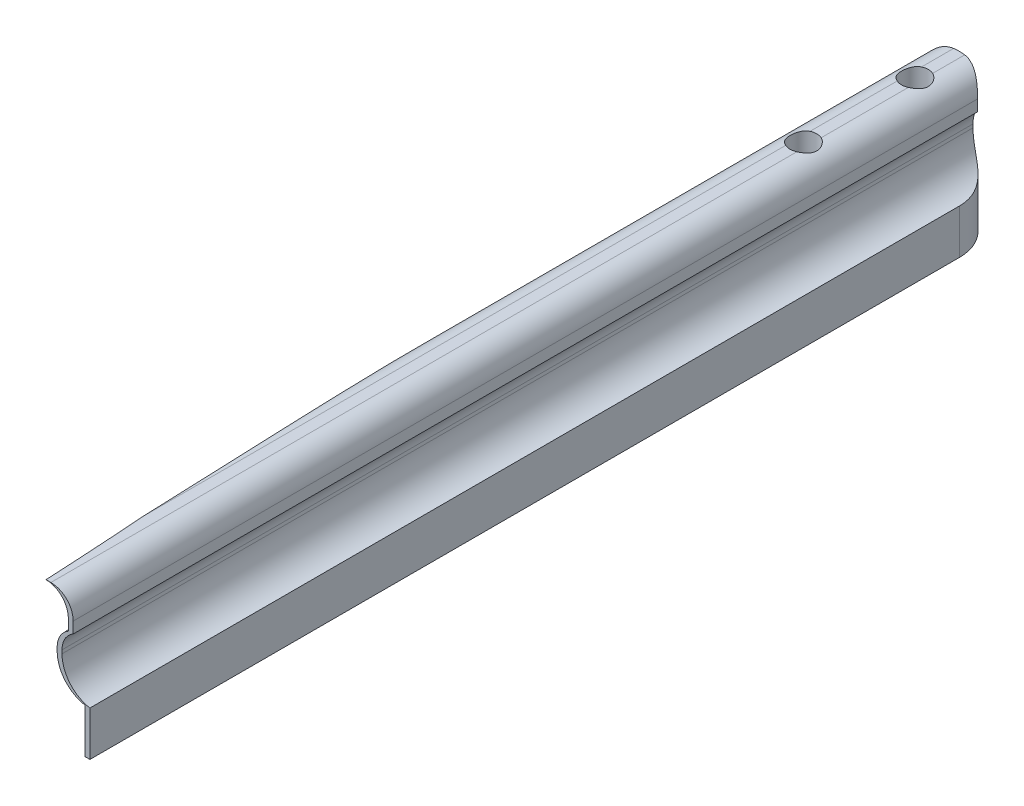
SolidWorks part; units mm, degrees
other "标注1"
sketch "草图3" plane through (-22.25, 4, -10) normal (-0.231, 0.6469, -0.7268) x (-0.9696, -0.2151, 0.1167)
other "标注2"
sketch "草图4" plane through (22.25, 8, -30) normal (0.0083, 0.0567, -0.9984) x (-0.9991, 0.0415, -0.0059)
ref_plane "前视基准面" through (0, 0, 0) normal (0, 0, 1) x (1, 0, 0)
ref_plane "上视基准面" through (0, 0, 0) normal (0, 1, 0) x (1, 0, 0)
ref_plane "右视基准面" through (0, 0, 0) normal (1, 0, 0) x (0, 0, -1)
other "Configuration Table"
sketch "草图1" plane through (0, 0, 0) normal (0, 1, 0) x (1, 0, 0)
  line L0 (-13.75, 12.5) -> (-13.75, -12.5)
  line L13 (-17.75, -12.5) -> (17.75, -12.5)
  line L21 (-17.75, -12.5) -> (-17.75, 12.5)
  line L22 (-17.75, 12.5) -> (17.75, 12.5)
  line L23 (17.75, -12.5) -> (17.75, 12.5)
  line L24 (-17.75, -12.5) -> (17.75, 12.5) construction
  line L25 (-17.75, 12.5) -> (17.75, -12.5) construction
  line L27 (13.75, 12.5) -> (13.75, -12.5)
  line L29 (-13.75, 0) -> (13.75, 0) construction
  line L32 (-22.25, 12.5) -> (22.25, 12.5)
  line L33 (-22.25, 12.5) -> (-22.25, 4.5)
  line L34 (-22.25, 4.5) -> (22.25, 4.5)
  line L35 (22.25, 12.5) -> (22.25, 4.5)
  point P0 (0, 0)
  point P15 (0, 4.5)
  dimension "D3" = 27.5
  dimension "D4" = 8
  dimension "D1" = 35.5
  dimension "D2" = 25
  dimension "D5" = 44.5
extrude "凸台-拉伸1" add sketch "草图1" along normal blind 4 contours L34 L21 L13 L0 | L34 L27 L13 L23 | L27 L34 L23 L22 | L21 L34 L0 L22 region at (-15.75, 0, -8.5) region at (-15.75, 0, 4) region at (15.75, 0, -8.5) region at (15.75, 0, 4)
extrude "凸台-拉伸2" add sketch "草图1<7>" along normal blind 3.5 contours L34 L35 L32 L33
sketch "草图1<7>" plane through (0, 0, 0) normal (0, 1, 0) x (1, 0, 0) same geometry as "草图1"
sketch "草图2" plane through (0, 0, -12.5) normal (0, 0, -1) x (-1, 0, 0)
  line L0 (18.25, 3.5) -> (22.25, 2)
  line L1 (22.25, 3.5) -> (18.25, 3.5)
  line L2 (22.25, 3.5) -> (22.25, 2)
  line L3 (22.25, 2) -> (18.25, 2) construction
  line L4 (18.25, 3.5) -> (18.25, 2) construction
  line L5 (-22.25, 2) -> (-18.25, 3.5)
  line L6 (-22.25, 3.5) -> (-18.25, 3.5)
  line L7 (-22.25, 3.5) -> (-22.25, 2)
  line L8 (-22.25, 2) -> (-18.25, 2) construction
  line L9 (-18.25, 3.5) -> (-18.25, 2) construction
  line L10 (13.75, 3.5) -> (-13.75, 3.5) construction
  line L11 (-13.25, 3.5) -> (-9.25, 3.5)
  line L12 (-13.25, 3.5) -> (-13.25, 2) construction
  line L13 (-13.25, 2) -> (-9.25, 2) construction
  line L14 (-9.25, 3.5) -> (-9.25, 2)
  line L15 (-13.75, 3.5) -> (-13.25, 3.5) construction
  line L16 (13.25, 3.5) -> (9.25, 3.5)
  line L17 (13.25, 3.5) -> (13.25, 2) construction
  line L18 (13.25, 2) -> (9.25, 2) construction
  line L19 (9.25, 3.5) -> (9.25, 2)
  line L20 (13.25, 3.5) -> (13.75, 3.5) construction
  line L21 (17.75, 3.5) -> (18.25, 3.5) construction
  line L22 (-13.25, 3.5) -> (-9.25, 2)
  line L23 (9.25, 2) -> (13.25, 3.5)
  line L24 (-9.25, 2) -> (9.25, 2)
  line L25 (-9.25, 3.5) -> (9.25, 3.5)
  line L26 (-15.75, 4) -> (-15.75, 6.5) construction
  line L27 (14.5, 8) -> (17, 8)
  line L28 (14.5, 8) -> (14.5, 6.5)
  line L29 (14.5, 6.5) -> (17, 6.5)
  line L30 (17, 8) -> (17, 6.5)
  line L31 (-17, 8) -> (-14.5, 8)
  line L32 (-17, 8) -> (-17, 6.5)
  line L33 (-17, 6.5) -> (-14.5, 6.5)
  line L34 (-14.5, 8) -> (-14.5, 6.5)
  line L35 (-13.75, 4) -> (-17.75, 4) construction
  line L36 (15.75, 6.5) -> (15.75, 4) construction
  line L37 (17.75, 4) -> (13.75, 4) construction
  line L38 (15, 6.5) -> (15, 4)
  line L39 (16.5, 6.5) -> (16.5, 4)
  line L40 (16.5, 4) -> (15.75, 4)
  line L41 (15.75, 4) -> (15, 4)
  line L42 (-16.5, 6.5) -> (-16.5, 4)
  line L43 (-16.5, 4) -> (-15.75, 4)
  line L44 (-15.75, 4) -> (-15, 4)
  line L45 (-15, 4) -> (-15, 6.5)
  line M9 (22.25, 3.5) -> (17.75, 3.5)
  line M11 (17.75, 4) -> (13.75, 4)
  line M13 (13.75, 3.5) -> (-13.75, 3.5)
  line M15 (-13.75, 4) -> (-17.75, 4)
  line M17 (-17.75, 3.5) -> (-22.25, 3.5)
  line M18 (-22.25, 3.5) -> (-22.25, 0)
  line M20 (22.25, 0) -> (22.25, 3.5)
  dimension "D1" = 4
  dimension "D2" = 1.5
  dimension "D3" = 2.5
  dimension "D4" = 1.5
  dimension "D5" = 2.5
  dimension "D6" = 1.5
extrude "切除-拉伸1" cut sketch "草图2" against normal through all contours L14 L24 L19 M13 | L19 L23 M13 | L22 L14 M13 | L5 M18 M17 | L0 M9 M20 region at (-20.9167, 3, -12.5) region at (20.9167, 3, -12.5) region at (10.5833, 3, -12.5) region at (0, 2.75, -12.5) region at (-10.5833, 3, -12.5)
extrude "凸台-拉伸4" add sketch "草图2<3>" against normal through all contours L34 L31 L32 L33 | L45 L33 L42 M15 | L30 L27 L28 L29 | L39 L29 L38 M11 region at (-15.75, 7.25, -12.5) region at (-15.75, 5.25, -12.5) region at (15.75, 7.25, -12.5) region at (15.75, 5.25, -12.5)
sketch "草图2<3>" plane through (0, 0, -12.5) normal (0, 0, -1) x (-1, 0, 0) same geometry as "草图2"
fillet "圆角1" radius 1 4 edges at (-16.5, 6.5, 0) (-15, 6.5, 0) (15, 6.5, 0) (16.5, 6.5, 0)
fillet "圆角2" radius 1.5 4 edges at (16.5, 4, 0) (15, 4, 0) (-15, 4, 0) (-16.5, 4, 0)
fillet "圆角3" radius 1 4 edges at (-17, 8, 0) (14.5, 8, 0) (17, 8, 0) (-14.5, 8, 0)
sketch "草图8" plane through (22.25, 0, 0) normal (1, 0, 0) x (0, 0, -1)
  line L0 (8.5, 0) -> (8.5, 18.5305)
  line L1 (12.5, 0) -> (4.5, 0) construction
mirror "镜向2" about plane through (0, 4, 12.5) normal (0, 0, -1) of bodies 192
sketch "草图10" plane through (0, 0, 0) normal (0, -1, 0) x (1, 0, 0)
  line L0 (-22.25, 29.5) -> (-17.75, 29.5) construction
  line L1 (-22.25, 37.5) -> (-17.75, 37.5)
  line L2 (-22.25, 37.5) -> (-22.25, 29.5)
  line L3 (-22.25, 29.5) -> (-17.75, 29.5)
  line L4 (-17.75, 37.5) -> (-17.75, 29.5)
  line L11 (-22.25, -4.5) -> (-17.75, -4.5) construction
  line L12 (-22.25, -12.5) -> (-17.75, -12.5)
  line L13 (-22.25, -12.5) -> (-22.25, -4.5)
  line L14 (-22.25, -4.5) -> (-17.75, -4.5)
  line L15 (-17.75, -12.5) -> (-17.75, -4.5)
  line L21 (-22.25, 37.5) -> (22.25, 37.5) construction
  line L22 (-13.75, 37.5) -> (22.25, 37.5)
  line L23 (-13.75, 37.5) -> (-13.75, -12.5)
  line L24 (-13.75, -12.5) -> (22.25, -12.5)
  line L25 (22.25, 37.5) -> (22.25, -12.5)
  line L26 (-22.25, -12.5) -> (22.25, -12.5) construction
  line L27 (-13.75, -4.5) -> (-13.75, 29.5) construction
extrude "切除-拉伸2" cut sketch "草图10" against normal through all
sketch "草图11" plane through (0, 0, 0) normal (0, -1, 0) x (-1, 0, 0)
  line L0 (17.75, -37.5) -> (17.75, 12.5) construction
  line L1 (13.75, 12.5) -> (13.75, -37.5) construction
  line L2 (17.75, 12.5) -> (13.75, 12.5) construction
  circle A0 centre (15.75, 10.5) radius 2
  line M2 (17.75, 12.5) -> (13.75, 12.5)
  line M3 (13.75, 12.5) -> (13.75, -37.5)
  line M5 (17.75, -37.5) -> (17.75, 12.5)
extrude "切除-拉伸3" cut sketch "草图11" against normal through all contours A0 M5 M2 | A0 M2 M3 region at (-17.3033, 0, -12.0533) region at (-14.1967, 0, -12.0533)
sketch "草图16" plane through (0, 0, 37.5) normal (0, 0, 1) x (1, 0, 0)
  line L8 (-17.75, 0) -> (-13.75, 0)
  line L9 (-13.75, 0) -> (-13.75, 4)
  line L10 (-15, 5.479) -> (-15, 5.634)
  line L11 (-14.5, 6.5) -> (-14.5, 7)
  line L12 (-15.5, 8) -> (-16, 8)
  line L13 (-17, 7) -> (-17, 6.5)
  line L14 (-16.5, 5.634) -> (-16.5, 5.479)
  line L15 (-17.75, 4) -> (-17.75, 0)
  line L16 (-17.75, 0) -> (-13.75, 0)
  line L17 (-13.75, 0) -> (-13.75, 4)
  line L18 (-15, 5.479) -> (-15, 5.634)
  line L19 (-14.5, 6.5) -> (-14.5, 7)
  line L20 (-15.5, 8) -> (-16, 8)
  line L21 (-17, 7) -> (-17, 6.5)
  line L22 (-16.5, 5.634) -> (-16.5, 5.479)
  line L23 (-17.75, 4) -> (-17.75, 0)
  arc A6 (-15, 5.479) -> (-13.75, 4) centre (-13.5, 5.479) ccw
  arc A7 (-14.5, 6.5) -> (-15, 5.634) centre (-14, 5.634) ccw
  arc A8 (-14.5, 7) -> (-15.5, 8) centre (-15.5, 7) ccw
  arc A9 (-16, 8) -> (-17, 7) centre (-16, 7) ccw
  arc A10 (-16.5, 5.634) -> (-17, 6.5) centre (-17.5, 5.634) ccw
  arc A11 (-17.75, 4) -> (-16.5, 5.479) centre (-18, 5.479) ccw
  arc A12 (-15, 5.479) -> (-13.75, 4) centre (-13.5, 5.479) ccw
  arc A13 (-14.5, 6.5) -> (-15, 5.634) centre (-14, 5.634) ccw
  arc A14 (-14.5, 7) -> (-15.5, 8) centre (-15.5, 7) ccw
  arc A15 (-16, 8) -> (-17, 7) centre (-16, 7) ccw
  arc A16 (-16.5, 5.634) -> (-17, 6.5) centre (-17.5, 5.634) ccw
  arc A17 (-17.75, 4) -> (-16.5, 5.479) centre (-18, 5.479) ccw
  dimension "D1" = 0
sketch "草图12" plane through (0, 0, 0) normal (0, -1, 0) x (1, 0, 0)
  line L0 (-17.75, 37.5) -> (-13.75, 37.5) construction
  line L1 (-17.75, 37.5) -> (-13.75, 37.5)
  line L2 (-17.75, 37.5) -> (-17.75, -12.5)
  line L3 (-17.75, -12.5) -> (-13.75, -12.5)
  line L4 (-13.75, 37.5) -> (-13.75, -12.5)
  line L5 (-17.75, 37.5) -> (-17.75, -10.5) construction
  arc A0 (-17.75, -10.5) -> (-13.75, -10.5) centre (-15.75, -10.5) ccw construction
extrude "切除-拉伸4" cut sketch "草图12" against normal blind 2
sketch "草图13" plane through (0, 8, 0) normal (0, 1, 0) x (1, 0, 0)
  line L0 (-16, 12.4843) -> (-16, -37.5) construction
  line L1 (-15.5, -37.5) -> (-15.5, 12.4843) construction
  line L2 (-15.75, 10.5) -> (-15.75, -22.774) construction
  circle A0 centre (-15.75, -22.774) radius 0.25
  circle A2 centre (-15.75, 10.5) radius 0.6
  arc A3 (-16, 12.4843) -> (-17, 12.0612) centre (-15.75, 10.5) ccw construction
  line M4 (-15.5, -37.5) -> (-15.5, 12.4843)
  line M7 (-16, -37.5) -> (-15.5, -37.5)
  dimension "D2" = 1.2
  dimension "D3" = 33.274
extrude "切除-拉伸5" cut sketch "草图13" against normal through all contours M4 M7 | A2 region at (-15.3558, 8, -10.5)
sketch "草图23" plane through (0, 0, 37.5) normal (0, 0, 1) x (1, 0, 0)
  line L0 (169.25, 37.7294) -> (169.25, -27.6564)
  line L16 (-17.75, 0) -> (-13.75, 0)
  line L17 (-13.75, 0) -> (-13.75, 4)
  line L18 (-15, 5.479) -> (-15, 5.634)
  line L19 (-14.5, 6.5) -> (-14.5, 7)
  line L20 (-15.5, 8) -> (-16, 8)
  line L21 (-17, 7) -> (-17, 6.5)
  line L22 (-16.5, 5.634) -> (-16.5, 5.479)
  line L23 (-17.75, 4) -> (-17.75, 0)
  arc A12 (-15, 5.479) -> (-13.75, 4) centre (-13.5, 5.479) ccw
  arc A13 (-14.5, 6.5) -> (-15, 5.634) centre (-14, 5.634) ccw
  arc A14 (-14.5, 7) -> (-15.5, 8) centre (-15.5, 7) ccw
  arc A15 (-16, 8) -> (-17, 7) centre (-16, 7) ccw
  arc A16 (-16.5, 5.634) -> (-17, 6.5) centre (-17.5, 5.634) ccw
  arc A17 (-17.75, 4) -> (-16.5, 5.479) centre (-18, 5.479) ccw
  dimension "D1" = 183
sketch "草图20" plane through (0, 2, 0) normal (0, -1, 0) x (1, 0, 0)
  line L0 (-15.75, -10.5) -> (-15.75, 22.7741)
  line L1 (-15.75, 13.2047) -> (-43.0541, 13.2047)
  line L2 (-17.75, 13.2047) -> (-15.75, 22.7741)
  line L3 (-17.75, 37.5) -> (-17.75, -10.5) construction
  line L4 (-15.75, 22.7741) -> (-8.4299, 22.7741)
  line L5 (-8.4299, 22.7741) -> (-8.4299, 31.2177)
  line L6 (-8.4299, 31.2177) -> (-21.8605, 31.2177)
  line L7 (-21.8605, 31.2177) -> (-21.8605, 13.2047)
  circle A2 centre (-15.75, -10.5) radius 0.6 construction
  dimension "D1" = 33.2741
  dimension "D2" = 23.7047
sketch "草图21" plane through (0, 8, 0) normal (0, 1, 0) x (1, 0, 0)
  line L0 (-15.75, 10.5) -> (-15.75, -51.8951)
  arc A0 (-15.5, 9.9546) -> (-15.5, 11.0454) centre (-15.75, 10.5) ccw construction
revolve "切除-旋转1" cut sketch "草图16" angle 360 about L0
sketch "草图24" plane through (0, 2, 0) normal (0, -1, 0) x (-1, 0, 0)
  circle A0 centre (15.75, 5.5) radius 0.6
  dimension "D2" = 1.2
  dimension "D1" = 5
extrude "切除-拉伸6" cut sketch "草图24" against normal through all
sketch "草图25" plane through (0, 8, 0) normal (0, 1, 0) x (1, 0, 0)
  line L0 (-17.75, -37.5) -> (-16.5, -37.5) construction
  line L1 (-18.1291, -34.2) -> (-8.5407, -34.2)
  line L2 (-18.1291, -34.2) -> (-18.1291, -37.5)
  line L3 (-18.1291, -37.5) -> (-8.5407, -37.5)
  line L4 (-8.5407, -34.2) -> (-8.5407, -37.5)
  dimension "D1" = 3.3
extrude "切除-拉伸7" cut sketch "草图25" against normal through all
sketch "草图26" plane through (0, 8, 0) normal (0, 1, 0) x (1, 0, 0)
  line L1 (-19.9573, -28.5) -> (-12.1103, -28.5)
  line L2 (-19.9573, -28.5) -> (-19.9573, -36.1764)
  line L3 (-19.9573, -36.1764) -> (-12.1103, -36.1764)
  line L4 (-12.1103, -28.5) -> (-12.1103, -36.1764)
  dimension "D1" = 39
extrude "切除-拉伸8" cut sketch "草图26" against normal through all
mirror "镜向3" about plane through (0, 0, 0) normal (1, 0, 0) of bodies 225
sketch "草图27" plane through (0, 0, 0) normal (1, 0, 0) x (0, 0, -1)
  line L1 (-53.4049, 28.074) -> (18.4538, 28.074)
  line L2 (-53.4049, 28.074) -> (-53.4049, -7.1426)
  line L3 (-53.4049, -7.1426) -> (18.4538, -7.1426)
  line L4 (18.4538, 28.074) -> (18.4538, -7.1426)
extrude "切除-拉伸9" cut sketch "草图27" against normal through all
